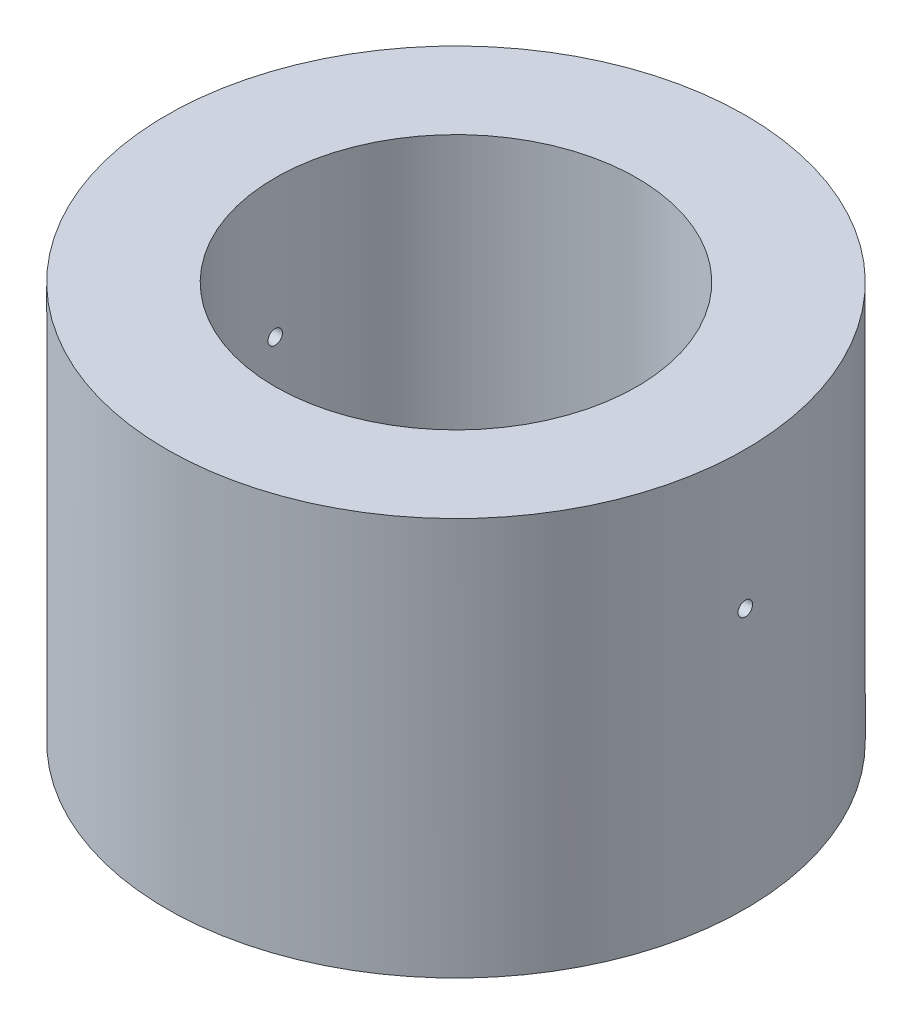
SolidWorks part; units mm, degrees
material "C (Graphite)"
ref_plane "Front Plane" through (0, 0, 0) normal (0, 0, 1) x (1, 0, 0)
ref_plane "Top Plane" through (0, 0, 0) normal (0, 1, 0) x (1, 0, 0)
ref_plane "Right Plane" through (0, 0, 0) normal (1, 0, 0) x (0, 0, -1)
sketch "Sketch1" plane through (0, 0, 0) normal (0, 1, 0) x (1, 0, 0)
  circle A0 centre (0, 0) radius 40
  circle A1 centre (0, 0) radius 25
  dimension "D1" = 80
  dimension "D2" = 50
extrude "Boss-Extrude1" add sketch "Sketch1" along normal blind 50
sketch "Sketch2" plane through (0, 0, 0) normal (0, -1, 0) x (1, 0, 0)
  circle A0 centre (0, 0) radius 37.5
  circle A1 centre (0, 0) radius 40
  dimension "D1" = 75
  dimension "D2" = 80
extrude "Boss-Extrude2" add sketch "Sketch2" along normal blind 5
sketch "Sketch3" plane through (0, 0, 0) normal (1, 0, 0) x (0, 0, -1)
  line L0 (40, 50) -> (-40, 50) construction
  circle A0 centre (0, 30.95) radius 1
  dimension "D1" = 2
  dimension "D2" = 19.05
extrude "Cut-Extrude2" cut sketch "Sketch3" against normal through all both and the other way through all
